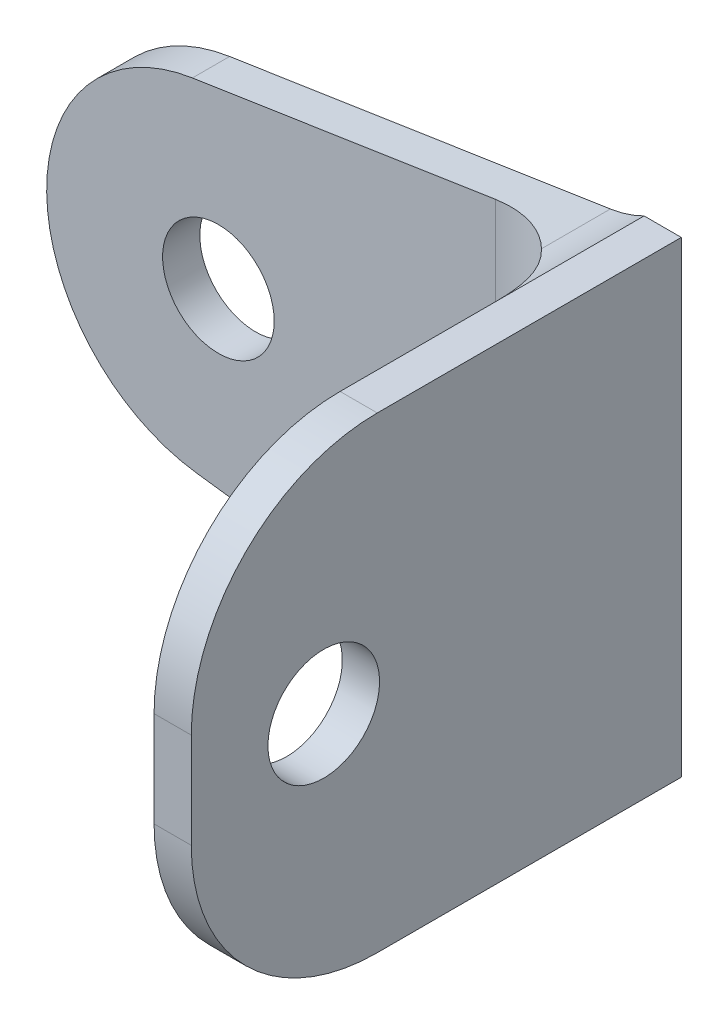
SolidWorks part; units mm, degrees
ref_plane "Front Plane" through (0, 0, 0) normal (0, 0, 1) x (1, 0, 0)
ref_plane "Top Plane" through (0, 0, 0) normal (0, 1, 0) x (1, 0, 0)
ref_plane "Right Plane" through (0, 0, 0) normal (1, 0, 0) x (0, 0, -1)
sketch "Sketch1" plane through (0, 0, 0) normal (0, 0, 1) x (1, 0, 0)
  line L0 (275, -59.9041) -> (250.7149, -63.6229)
  line L1 (275, -380) -> (275, 0) construction
  line L2 (250.921, -81.9038) -> (275, -85.0372)
  line L3 (275, -85.0372) -> (275, -59.9041)
  line L4 (275, 120) -> (275, -379.2634) construction
  arc A0 (250.7149, -63.6229) -> (250.921, -81.9038) centre (252.1123, -72.7488) ccw
extrude "Boss-Extrude1" add sketch "Sketch1" along normal blind 2
sketch "Sketch2" plane through (275, 0, 0) normal (-1, 0, 0) x (0, 0, 1)
  line L0 (0, -59.9041) -> (2, -59.9041)
  line L2 (0, -59.9041) -> (0, -63.6229) construction
  line L3 (2, -59.9041) -> (26.3463, -59.9041)
  line L4 (26.3463, -59.9041) -> (26.3463, -85.0372)
  line L5 (26.3463, -85.0372) -> (0, -85.0372)
  line L6 (0, -85.0372) -> (0, -59.9041)
  line L7 (2, -59.9041) -> (0, -59.9041) construction
extrude "Boss-Extrude2" add sketch "Sketch2" along normal blind 2
fillet "Fillet1" radius 10 2 edges at (274, -59.9041, 26.3463) (274, -85.0372, 26.3463)
fillet "Fillet2" radius 6 3 edges at (273, -84.777, 1) (273, -72.4937, 2) (273, -60.2104, 1)
sketch "Sketch3" plane through (0, 0, 2) normal (0, 0, 1) x (1, 0, 0)
  circle A0 centre (252.1123, -72.7488) radius 3
  arc A1 (250.7149, -63.6229) -> (250.921, -81.9038) centre (252.1123, -72.7488) ccw construction
  dimension "D1" = 6
extrude "Cut-Extrude1" cut sketch "Sketch3" against normal up to next
sketch "Sketch4" plane through (273, 0, 0) normal (-1, 0, 0) x (0, 0, 1)
  line L0 (26.3463, -72.4707) -> (8, -72.4707) construction
  line L1 (26.3463, -75.0372) -> (26.3463, -69.9041) construction
  line L2 (8, -59.9041) -> (8, -85.0372) construction
  line L3 (8, -72.4707) -> (17.1732, -72.4707) construction
  circle A0 centre (19.2241, -72.4707) radius 3
  dimension "D1" = 6
extrude "Cut-Extrude2" cut sketch "Sketch4" against normal up to next
